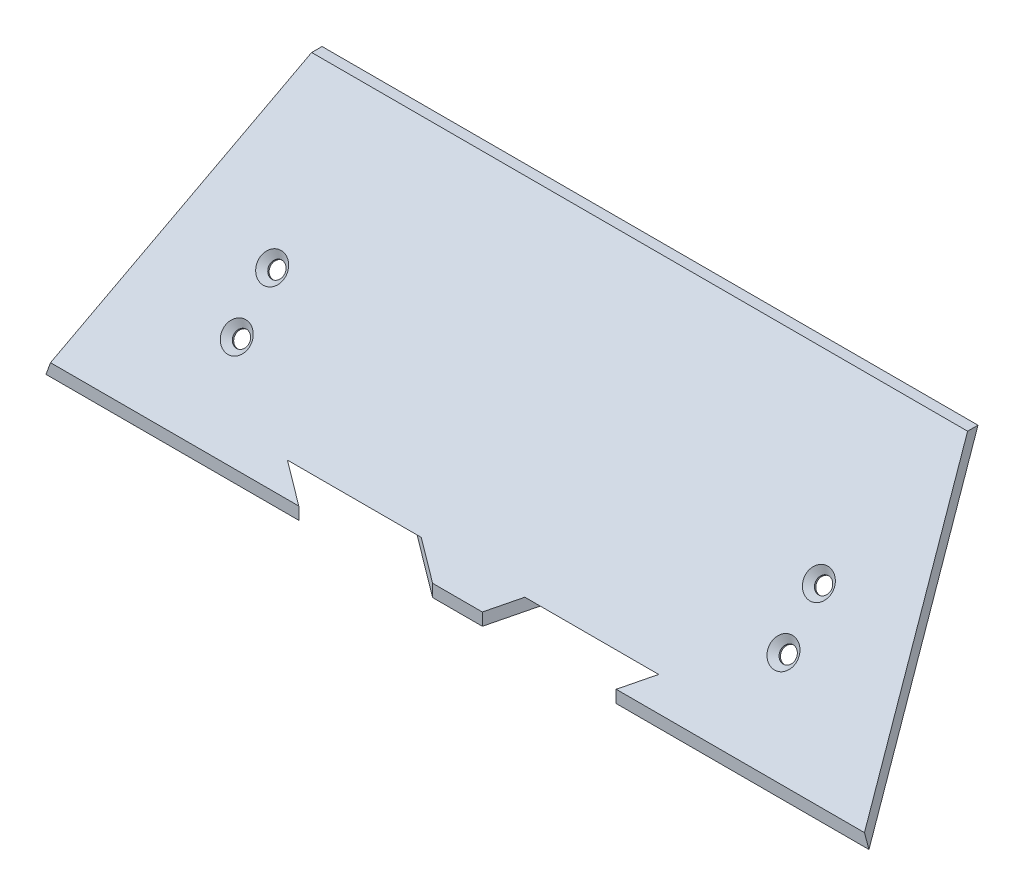
SolidWorks part; units mm, degrees
material "Delrin 2700 NC010, Low Viscosity Acetal Copolymer (SS)"
ref_plane "Front Plane" through (0, 0, 0) normal (0, 0, 1) x (1, 0, 0)
ref_plane "Top Plane" through (0, 0, 0) normal (0, 1, 0) x (1, 0, 0)
ref_plane "Right Plane" through (0, 0, 0) normal (1, 0, 0) x (0, 0, -1)
sketch "Sketch2" plane through (0, 0, 0) normal (1, 0, 0) x (0, 0, -1)
  line L0 (0, 0) -> (-2.3622, 0)
  line L1 (-2.3622, 0) -> (45.4805, 57.0167)
  line L2 (45.4805, 57.0167) -> (47.8427, 57.0167)
  line L3 (47.8427, 57.0167) -> (0, 0)
  dimension "D1" = 50
  dimension "D2" = 74.43
  dimension "D3" = 2.3622
extrude "Boss-Extrude1" add sketch "Sketch2" along normal blind 186.9479
sketch "Sketch3" plane through (0, 0, 0) normal (-1, 0, 0) x (0, 0, 1)
  line L0 (-4.1057, 4.893) -> (-4.1057, 7.7082)
  line L1 (-45.4805, 57.0167) -> (2.3622, 0) construction
  line L2 (-4.1057, 7.7082) -> (2.3622, 0)
  line L3 (2.3622, 0) -> (0, 0)
  line L4 (0, 0) -> (-4.1057, 4.893)
  line L5 (0, 0) -> (-47.8427, 57.0167) construction
  line L6 (-4.1057, 4.893) -> (-4.1057, -12.9833) construction
extrude "Cut-Extrude1" cut sketch "Sketch3" against normal through all
sketch "Sketch4" plane through (93.4965, -1.9814, -4.1057) normal (0, 0, -1) x (-1, 0, 0)
  line L0 (93.4965, 58.998) -> (74.525, 58.998)
  line L1 (-93.4515, 58.998) -> (93.4965, 58.998) construction
  line L3 (74.525, 58.998) -> (93.4965, 6.8743)
  line L4 (93.4965, 6.8743) -> (93.4965, 58.998)
  line L5 (-93.4515, 6.8743) -> (-93.4515, 58.998)
  line L6 (-93.4515, 58.998) -> (-74.48, 58.998)
  line L7 (-74.48, 58.998) -> (-93.4515, 6.8743)
  dimension "D1" = 20
  dimension "D2" = 20
extrude "Cut-Extrude2" cut sketch "Sketch4" along normal through all
hole_wizard "CSK for M3 Flat Head Machine Screw1" positions "Sketch5" profile "Sketch6" countersink size "M3" standard "ANSI Metric"
sketch "Sketch5" plane through (0, 1.1632, 1.3862) normal (0, 0.6428, 0.766) x (1, 0, 0)
  point P0 (31.3777, 39.6549)
  point P2 (31.3777, 27.1455)
sketch "Sketch6" plane through (31.3777, 31.5406, -24.1035) normal (1, 0, 0) x (0, -0.766, 0.6428)
  line L0 (0, 0) -> (0, 5)
  line L1 (0, 5) -> (1.75, 5)
  line L2 (1.75, 5) -> (1.75, 1.4)
  line L3 (1.75, 1.4) -> (3.15, 0)
  line L5 (3.15, 0) -> (0, 0)
  line L6 (-1.75, 1.4) -> (-3.15, 0) construction
  line L10 (0, 5) -> (-1.75, 5) construction
  line L11 (0, -6.35) -> (0, 107.95) construction
  dimension "Hole Dia." = 3.5
  dimension "Hole Depth" = 5
  dimension "Near C'Sink Dia." = 6.3
  dimension "Near C'Sink Angle" = 90
  dimension "Drill Angle" = 180
ref_plane "Plane1" through (93.474, 0, 0) normal (1, 0, 0) x (0, 0, -1)
mirror "Mirror1" about plane through (93.474, 0, 0) normal (1, 0, 0) of "CSK for M3 Flat Head Machine Screw1"
ref_plane "Plane2" through (112.633, 0, -65.0287) normal (-0.866, 0, 0.5) x (0.5, 0, 0.866)
sketch "Sketch7" plane through (112.633, 0, -65.0287) normal (-0.866, 0, 0.5) x (0.5, 0, 0.866)
  line L0 (46.0064, 4.9186) -> (46.0064, 3.9186)
  line L1 (61.2064, 11.9186) -> (46.0064, 11.9186)
  line L2 (61.2064, 11.9186) -> (61.2064, 4.9186)
  line L3 (61.2064, 4.9186) -> (46.0064, 4.9186)
  line L4 (46.0064, 11.9186) -> (46.0064, 4.9186)
  line L5 (46.0064, 3.9186) -> (61.2064, 3.9186)
  line L6 (61.2064, 3.9186) -> (61.2064, 4.9186)
  dimension "D1" = 1
extrude "Cut-Extrude3" cut sketch "Sketch7" along normal up to surface (8.7674 mm away) contours L1 L4 L3 L2 | L5 L6 L3 L0 region at (139.4362, 4.4186, -18.6042) region at (139.4362, 8.4186, -18.6042) up to face at (155.5703, 29.1276, -22.0787)
mirror "Mirror2" about plane through (93.474, 0, 0) normal (1, 0, 0) of "Cut-Extrude3"
